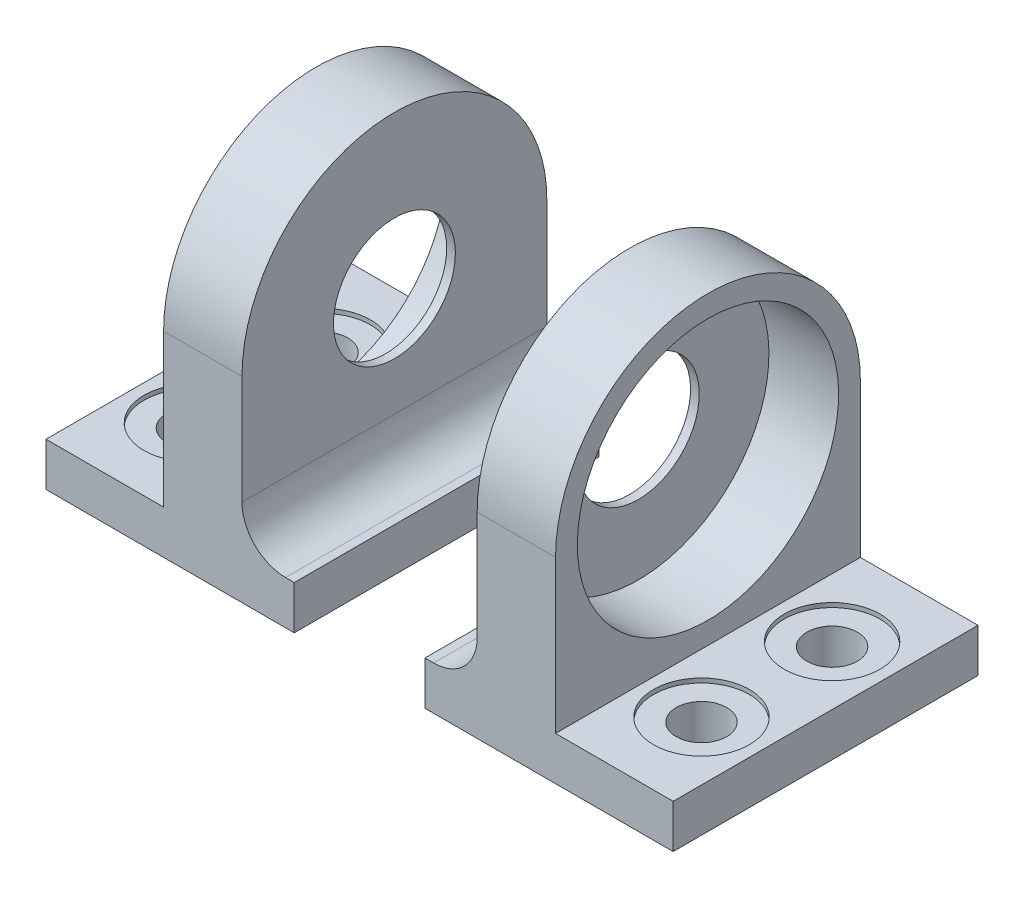
SolidWorks part; units mm, degrees
ref_plane "前视基准面" through (0, 0, 0) normal (0, 0, 1) x (1, 0, 0)
ref_plane "上视基准面" through (0, 0, 0) normal (0, 1, 0) x (1, 0, 0)
ref_plane "右视基准面" through (0, 0, 0) normal (1, 0, 0) x (0, 0, -1)
sketch "草图2" plane through (0, 0, 0) normal (0, 0, 1) x (1, 0, 0)
  line L0 (13.5, 50.0954) -> (13.5, -14.4699) construction
  line L1 (0, 0) -> (-8.0625, 0)
  line L2 (0, 5) -> (0, 40)
  line L3 (0, 40) -> (-9, 40)
  line L4 (-9, 5) -> (-9, 40)
  line L5 (-8.0625, 0) -> (-22.5, 0)
  line L7 (-9, 5) -> (-22.5, 5)
  line L8 (-22.5, 0) -> (-22.5, 5)
  line L9 (49.5, 0) -> (49.5, 5)
  line L10 (36, 5) -> (49.5, 5)
  line L11 (35.0625, 0) -> (49.5, 0)
  line L12 (36, 5) -> (36, 40)
  line L13 (27, 40) -> (36, 40)
  line L14 (27, 5) -> (27, 40)
  line L15 (27, 0) -> (35.0625, 0)
  line L17 (0, 0) -> (6, 0)
  line L19 (0, 5) -> (6, 5)
  line L20 (6, 0) -> (6, 5)
  line L21 (27, 0) -> (21, 0)
  line L23 (27, 5) -> (21, 5)
  line L24 (21, 0) -> (21, 5)
  dimension "D1" = 40
  dimension "D2" = 9
  dimension "D3" = 5
  dimension "D4" = 22.5
  dimension "D5" = 27
  dimension "D6" = 6
  dimension "D7" = 6
extrude "凸台-拉伸2" add sketch "草图2" along normal blind 35
sketch "草图4" plane through (36, 0, 0) normal (1, 0, 0) x (0, 0, -1)
  line L0 (-35, 22.5) -> (-35, 40)
  line L3 (-35, 40) -> (0, 40)
  line L5 (0, 40) -> (0, 22.5)
  circle A0 centre (-17.5, 22.5) radius 17.5
  line M2 (0, 5) -> (0, 40)
  line M3 (0, 40) -> (-35, 40)
  line M4 (-35, 40) -> (-35, 5)
extrude "切除-拉伸11" cut sketch "草图4" against normal blind 9 contours A0 L3 M4 | A0 M2 M3 region at (36, 36.0911, 31.0911) region at (36, 36.0911, 3.9089)
sketch "草图5" plane through (-9, 0, 0) normal (-1, 0, 0) x (0, 0, 1)
  line L0 (0, 22.5) -> (0, 40)
  line L3 (0, 40) -> (35, 40)
  line L6 (35, 40) -> (35, 22.5)
  circle A0 centre (17.5, 22.5) radius 17.5
  line M2 (0, 40) -> (0, 5)
  line M4 (35, 5) -> (35, 40)
  line M5 (35, 40) -> (0, 40)
extrude "切除-拉伸12" cut sketch "草图5" against normal blind 9 contours A0 L3 M2 | A0 M4 M5 region at (-9, 36.0911, 3.9089) region at (-9, 36.0911, 31.0911)
sketch "草图6" plane through (-9, 0, 0) normal (-1, 0, 0) x (0, 0, 1)
  circle A0 centre (17.5, 22.5) radius 15
extrude "切除-拉伸13" cut sketch "草图6" against normal blind 8
sketch "草图7" plane through (36, 0, 0) normal (1, 0, 0) x (0, 0, -1)
  circle A0 centre (-17.5, 22.5) radius 15
extrude "切除-拉伸15" cut sketch "草图7" against normal blind 8
sketch "草图16" plane through (27, 0, 0) normal (-1, 0, 0) x (0, 0, 1)
  circle A0 centre (17.5, 22.5) radius 7
extrude "切除-拉伸18" cut sketch "草图16" against normal blind 1
sketch "草图17" plane through (0, 0, 0) normal (1, 0, 0) x (0, 0, -1)
  circle A0 centre (-17.5, 22.5) radius 7
extrude "切除-拉伸19" cut sketch "草图17" against normal blind 1
ref_axis "基准轴1" through (28, 22.5, 17.5) along (-1, 0, 0)
sketch "草图19" plane through (0, 5, 0) normal (0, 1, 0) x (1, 0, 0)
  line L0 (42.75, -35) -> (42.75, 0)
  line L1 (49.5, -35) -> (36, -35) construction
  line L2 (49.5, 0) -> (36, 0) construction
  line L3 (-15.75, 0) -> (-15.75, -35)
  line L4 (-9, 0) -> (-22.5, 0) construction
  line L5 (-9, -35) -> (-22.5, -35) construction
  point P6 (42.75, -10)
  point P7 (42.75, -25)
  point P14 (-15.75, -10)
  point P15 (-15.75, -25)
  dimension "D1" = 10
  dimension "D2" = 10
hole_wizard "打孔尺寸(%根据六角头螺)栓 C 级的类型1" positions "3D草图1" profile "草图20" counterbore size "M5" standard "GB"
sketch3d "3D草图1"
  point P0 (-15.75, 5, 10)
  point P3 (-15.75, 5, 25)
  point P6 (42.75, 5, 10)
  point P9 (42.75, 5, 25)
sketch "草图20" plane through (-15.75, 5, 10) normal (1, 0, 0) x (0, 0, 1)
  line L0 (0, 0) -> (0, 6.7425)
  line L1 (0, 6.7425) -> (2.9, 5)
  line L2 (2.9, 5) -> (2.9, 0.5)
  line L3 (2.9, 0.5) -> (5.5, 0.5)
  line L4 (5.5, 0.5) -> (5.5, 0)
  line L5 (5.5, 0) -> (0, 0)
  line L10 (0, 6.7425) -> (-2.9, 5) construction
  line L11 (0, -6.35) -> (0, 107.95) construction
  dimension "孔直径" = 5.8
  dimension "孔深度" = 5
  dimension "柱形沉头孔直径" = 11
  dimension "柱形沉头孔深度" = 0.5
  dimension "导头角度" = 118
fillet "圆角3" radius 5 1 edges at (27, 5, 17.5)
fillet "圆角4" radius 5 1 edges at (0, 5, 17.5)
